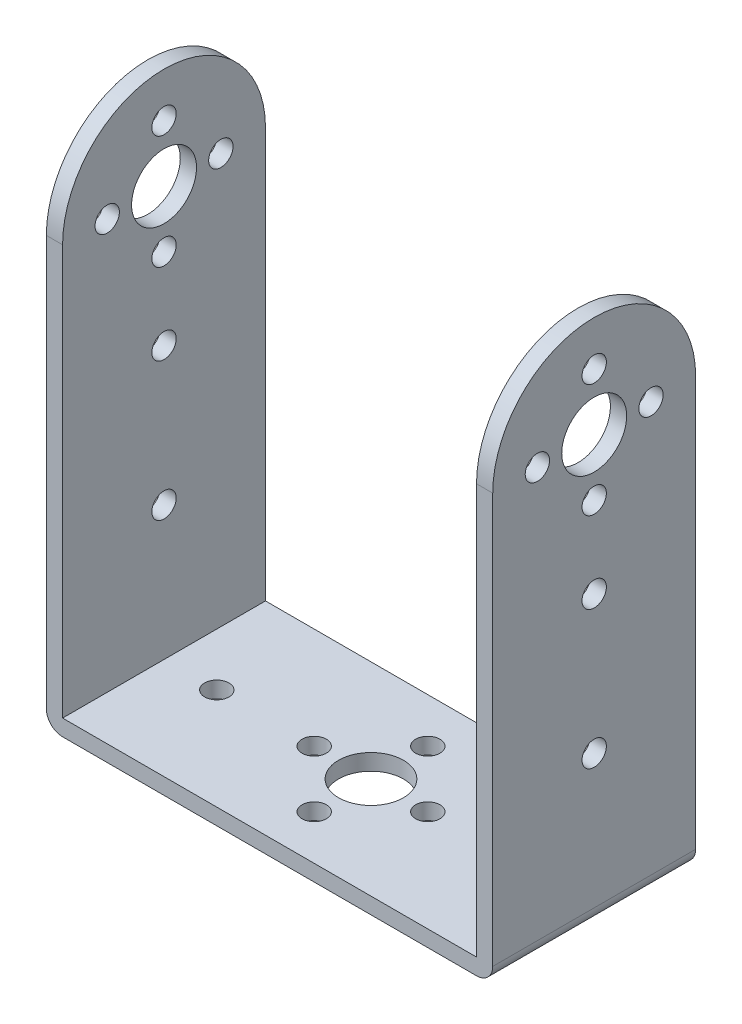
SolidWorks part; units mm, degrees
ref_plane "Piano frontale" through (0, 0, 0) normal (0, 0, 1) x (1, 0, 0)
ref_plane "Piano superiore" through (0, 0, 0) normal (0, 1, 0) x (1, 0, 0)
ref_plane "Piano destro" through (0, 0, 0) normal (1, 0, 0) x (0, 0, -1)
sketch "Schizzo4" plane through (0, 0, 0) normal (0, 0, 1) x (1, 0, 0)
  line L0 (-48.7225, 30.4956) -> (-48.7225, -34.5044)
  line L1 (-48.7225, -34.5044) -> (6.2775, -34.5044)
  line L2 (6.2775, -34.5044) -> (6.2775, 30.4956)
  line L3 (6.2775, 30.4956) -> (4.2775, 30.4956)
  line L4 (4.2775, 30.4956) -> (4.2775, -32.5044)
  line L5 (4.2775, -32.5044) -> (-46.7225, -32.5044)
  line L6 (-46.7225, -32.5044) -> (-46.7225, 30.4956)
  line L7 (-46.7225, 30.4956) -> (-48.7225, 30.4956)
  dimension "D1" = 65
  dimension "D2" = 55
  dimension "D3" = 2
  dimension "D4" = 2
extrude "Estrusione-Estrusione1" add sketch "Schizzo4" along normal blind 25
fillet "Raccordo1" radius 2 1 edges at (6.2775, -34.5044, 12.5)
fillet "Raccordo2" radius 2 1 edges at (-48.7225, -34.5044, 12.5)
sketch "Schizzo8" plane through (6.2775, 0, 0) normal (1, 0, 0) x (0, 0, -1)
  line L0 (-12.5, 30.4956) -> (-12.5, -32.5044) construction
  line L1 (0, -32.5044) -> (-25, -32.5044) construction
  line L2 (0, 17.9956) -> (-25, 17.9956) construction
  line L3 (0, -32.5044) -> (0, 30.4956) construction
  line L11 (-25, 30.4956) -> (-25, -32.5044)
  line L12 (-25, -32.5044) -> (0, -32.5044)
  line L13 (0, -32.5044) -> (0, 30.4956)
  line L14 (0, 30.4956) -> (-25, 30.4956)
  line L15 (-25, 30.4956) -> (-25, 17.9956)
  line L17 (0, 17.9956) -> (0, 30.4956)
  line L18 (0, 30.4956) -> (-25, 30.4956)
  arc A0 (0, 17.9956) -> (-25, 17.9956) centre (-12.5, 17.9956) ccw
  circle A1 centre (-12.5, 17.9956) radius 4
  circle A2 centre (-5.5, 17.9956) radius 1.5
  circle A3 centre (-12.5, 24.9956) radius 1.5
  circle A4 centre (-19.5, 17.9956) radius 1.5
  circle A5 centre (-12.5, 0.9956) radius 1.5
  circle A6 centre (-12.5, -16.0044) radius 1.5
  circle A7 centre (-12.5, 10.9956) radius 1.5
  point P1 (-12.5, 30.4956)
  point P8 (0, 17.9956)
  point P11 (-25, 17.9956)
  line M2 (-25, 30.4956) -> (-25, -32.5044)
  line M4 (0, -32.5044) -> (0, 30.4956)
  line M5 (0, 30.4956) -> (-25, 30.4956)
  dimension "D1" = 0
  dimension "D5" = 8
  dimension "D7" = 3
  dimension "D8" = 3
  dimension "D9" = 3
  dimension "D10" = 3
  dimension "D11" = 3
  dimension "D12" = 3
  dimension "D2" = 7
  dimension "D3" = 7
  dimension "D4" = 7
  dimension "D6" = 7
  dimension "D13" = 17
  dimension "D14" = 17
  dimension "D15" = 16.5
  dimension "D16" = 12.5
  dimension "D17" = 12.5
  dimension "D18" = 5.5
extrude "Taglio-Estrusione5" cut sketch "Schizzo8" against normal through all both and the other way through all contours A0 M4 M5 | A0 L18 M2 region at (6.2775, 27.7035, 22.2079) region at (6.2775, 27.7035, 2.7921)
extrude "Taglio-Estrusione6" cut sketch "Schizzo8<9>" against normal through all both and the other way through all contours A4 | A1 | A3 | A2 | A7 | A5 | A6 region at (6.2775, 17.9956, 12.5) region at (6.2775, 17.9956, 5.5) region at (6.2775, 24.9956, 12.5) region at (6.2775, 17.9956, 19.5) region at (6.2775, 0.9956, 12.5) region at (6.2775, -16.0044, 12.5) region at (6.2775, 10.9956, 12.5)
sketch "Schizzo8<9>" plane through (6.2775, 0, 0) normal (1, 0, 0) x (0, 0, -1) same geometry as "Schizzo8"
sketch "Schizzo11" plane through (0, -32.5044, 0) normal (0, 1, 0) x (1, 0, 0)
  line L0 (-46.7225, -12.5) -> (4.2775, -12.5) construction
  line L1 (-46.7225, -25) -> (-46.7225, 0) construction
  line L2 (4.2775, -25) -> (4.2775, 0) construction
  line L3 (-21.2225, 0) -> (-21.2225, -25) construction
  line L4 (4.2775, 0) -> (-46.7225, 0) construction
  line L5 (4.2775, -25) -> (-46.7225, -25) construction
  circle A0 centre (-21.2225, -12.5) radius 4
  circle A1 centre (-21.2225, -5.5) radius 1.5
  circle A2 centre (-28.2225, -12.5) radius 1.5
  circle A3 centre (-21.2225, -19.5) radius 1.5
  circle A4 centre (-14.2225, -12.5) radius 1.5
  circle A5 centre (-2.2225, -12.5) radius 1.5
  circle A6 centre (-40.2225, -12.5) radius 1.5
  dimension "D1" = 8
  dimension "D2" = 3
  dimension "D3" = 3
  dimension "D4" = 3
  dimension "D5" = 3
  dimension "D6" = 3
  dimension "3" = 3
  dimension "D8" = 7
  dimension "D9" = 7
  dimension "D10" = 7
  dimension "D11" = 7
  dimension "D12" = 12
  dimension "D13" = 12
extrude "Taglio-Estrusione7" cut sketch "Schizzo11" against normal through all both contours A6 | A2 | A0 | A4 | A1 | A3 | A5
